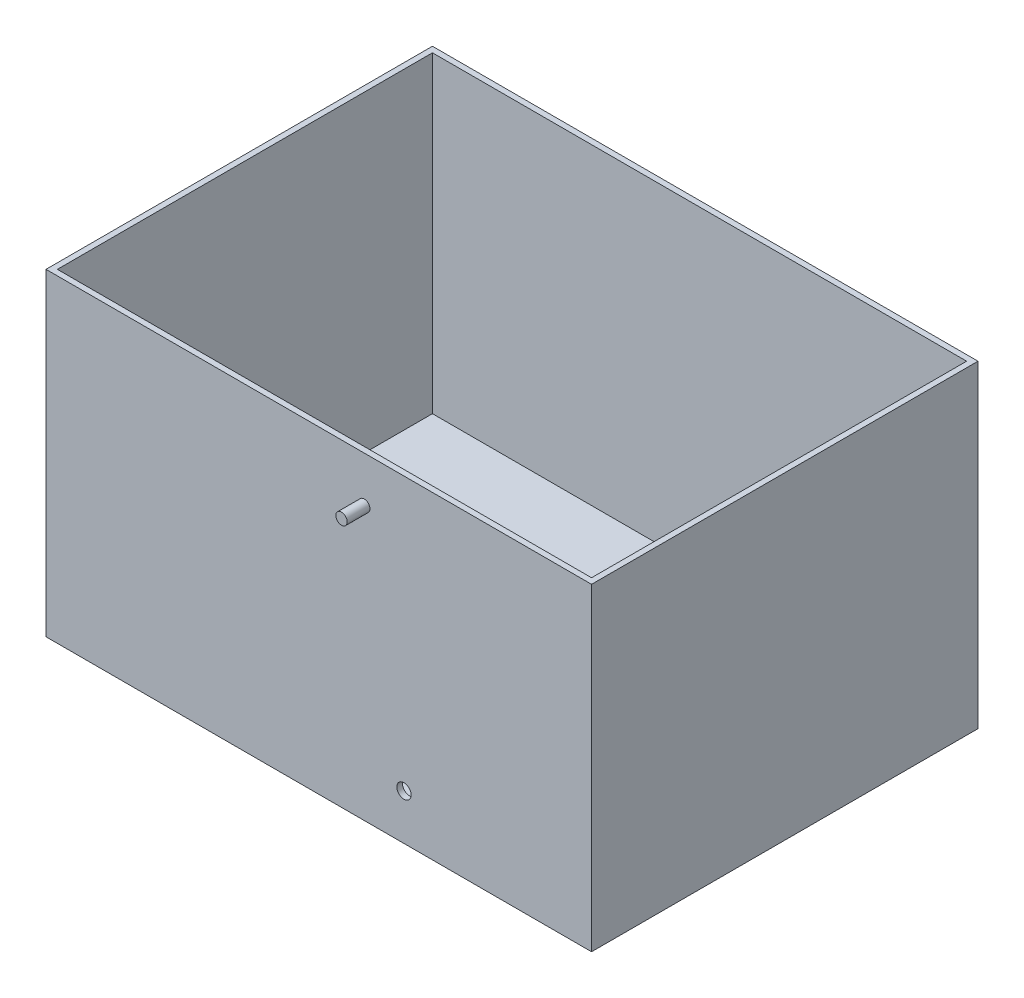
SolidWorks part; units mm, degrees
ref_plane "Front Plane" through (0, 0, 0) normal (0, 0, 1) x (1, 0, 0)
ref_plane "Top Plane" through (0, 0, 0) normal (0, 1, 0) x (1, 0, 0)
ref_plane "Right Plane" through (0, 0, 0) normal (1, 0, 0) x (0, 0, -1)
sketch "Sketch1" plane through (0, 0, 0) normal (0, 1, 0) x (1, 0, 0)
  line L0 (-149.225, 107.95) -> (-149.225, 104.775) construction
  line L1 (-152.4, 107.95) -> (152.4, 107.95)
  line L2 (-152.4, 107.95) -> (-152.4, -107.95)
  line L3 (-152.4, -107.95) -> (152.4, -107.95)
  line L4 (152.4, 107.95) -> (152.4, -107.95)
  line L5 (-152.4, 107.95) -> (152.4, -107.95) construction
  line L6 (-152.4, -107.95) -> (152.4, 107.95) construction
  line L7 (-149.225, -104.775) -> (149.225, -104.775)
  line L8 (-149.225, -104.775) -> (-149.225, 104.775)
  line L9 (-149.225, 104.775) -> (149.225, 104.775)
  line L10 (149.225, -104.775) -> (149.225, 104.775)
  line L11 (-149.225, -104.775) -> (149.225, 104.775) construction
  line L12 (-149.225, 104.775) -> (149.225, -104.775) construction
  line L13 (-149.225, 104.775) -> (-152.4, 104.775) construction
  point P0 (0, 0)
  point P6 (0, 0)
  dimension "D1" = 304.8
  dimension "D2" = 215.9
  dimension "D3" = 3.175
extrude "Boss-Extrude1" add sketch "Sketch1" along normal blind 3.175 contours L7 L10 L9 L8 region at (0, 0, 0)
extrude "Boss-Extrude2" add sketch "Sketch1<3>" along normal blind 177.8
sketch "Sketch1<3>" plane through (0, 0, 0) normal (0, 1, 0) x (1, 0, 0) same geometry as "Sketch1"
sketch "Sketch2" plane through (0, 0, 107.95) normal (0, 0, 1) x (1, 0, 0)
  line L0 (25.4, 152.4) -> (152.4, 152.4) construction
  line L1 (152.4, 177.8) -> (152.4, 0) construction
  line L2 (25.4, 152.4) -> (25.4, 177.8) construction
  line L3 (-152.4, 177.8) -> (152.4, 177.8) construction
  line L4 (-152.4, 25.4) -> (47.6, 25.4) construction
  line L10 (-152.4, 177.8) -> (-152.4, 0) construction
  line L11 (47.6, 25.4) -> (47.6, 0) construction
  line L12 (-152.4, 0) -> (152.4, 0) construction
  circle A0 centre (25.4, 152.4) radius 3.175
  circle A1 centre (47.6, 25.4) radius 4
  dimension "D1" = 6.35
  dimension "D4" = 8
  dimension "D2" = 25.4
  dimension "D3" = 127
  dimension "D5" = 25.4
  dimension "D6" = 200
extrude "Boss-Extrude3" add sketch "Sketch2" along normal blind 12.7 contours A0
extrude "Cut-Extrude1" cut sketch "Sketch2<3>" against normal through all both and the other way through all contours A1 region at (47.6, 25.4, 107.95)
sketch "Sketch2<3>" plane through (0, 0, 107.95) normal (0, 0, 1) x (1, 0, 0) same geometry as "Sketch2"
mirror "Mirror1" about plane through (0, 0, 0) normal (0, 0, 1) of "Boss-Extrude3"
